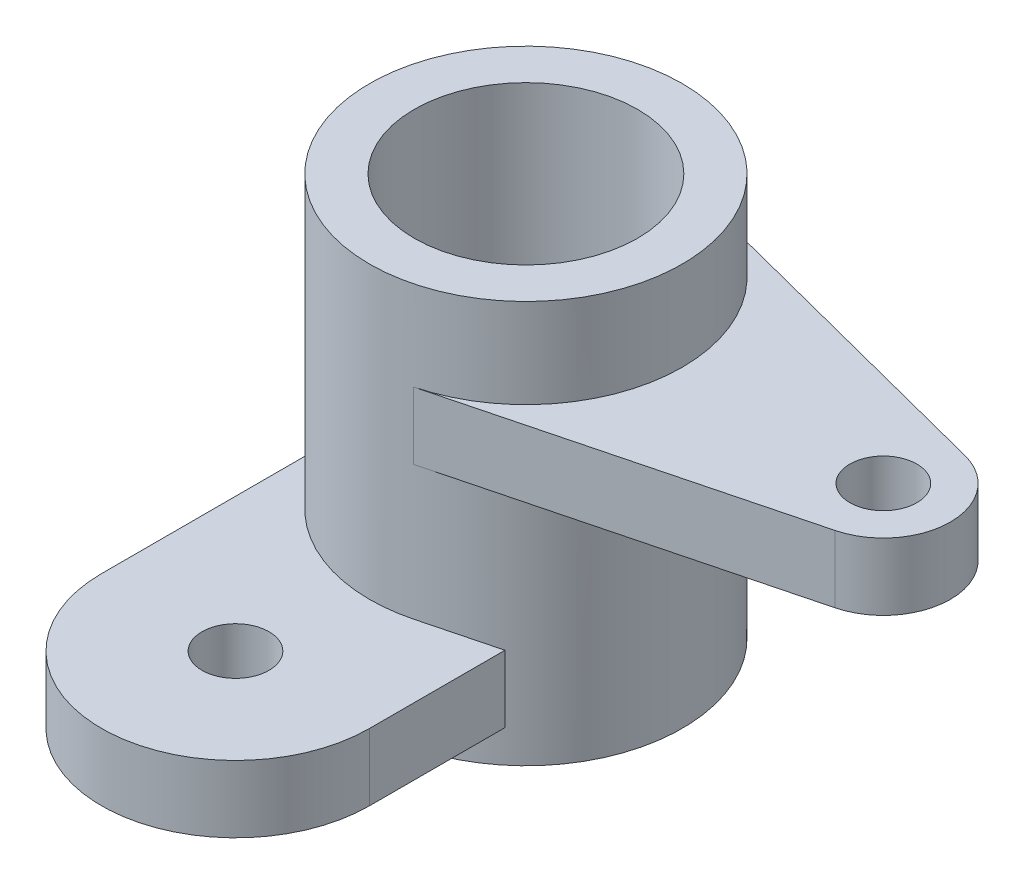
SolidWorks part; units mm, degrees
ref_plane "Front Plane" through (0, 0, 0) normal (0, 0, 1) x (1, 0, 0)
ref_plane "Top Plane" through (0, 0, 0) normal (0, 1, 0) x (1, 0, 0)
ref_plane "Right Plane" through (0, 0, 0) normal (1, 0, 0) x (0, 0, -1)
sketch "Sketch1" plane through (0, 0, 0) normal (0, 1, 0) x (1, 0, 0)
  line L0 (0, 0) -> (50000, 0) construction
  line L1 (0, 0) -> (0, 50000) construction
  line L2 (25, -60) -> (25, -24.4949)
  line L3 (-35, -60) -> (-35, 0)
  line L4 (83.75, -14.5237) -> (8.75, -33.8886)
  line L5 (83.75, 14.5237) -> (8.75, 33.8886)
  circle A0 centre (0, 0) radius 25
  circle A1 centre (0, 0) radius 35
  circle A2 centre (80, 0) radius 7.5
  circle A3 centre (80, 0) radius 15
  circle A4 centre (-5, -60) radius 7.5
  arc A5 (-35, -60) -> (25, -60) centre (-5, -60) ccw
  dimension "D1" = 70
  dimension "D2" = 50
  dimension "D3" = 30
  dimension "D4" = 15
  dimension "D6" = 5
  dimension "D7" = 60
  dimension "D8" = 15
  dimension "D5" = 80
  dimension "D9" = 60
extrude "Boss-Extrude1" add sketch "Sketch1" against normal blind 90 contours A1 A0 region at (17.021, 0, 29.4443)
extrude "Boss-Extrude2" add sketch "Sketch1<3>" against normal blind 15 from offset 20 contours A3 A2 | A3 A1 | A1 L4 L2 region at (21.0932, 0, 29.1879) region at (48.3793, 0, -0.4187) region at (65.4243, 0, 0) offset against normal yes
sketch "Sketch1<3>" plane through (0, 0, 0) normal (0, 1, 0) x (1, 0, 0) same geometry as "Sketch1"
extrude "Boss-Extrude3" add sketch "Sketch1<4>" against normal blind 15 from offset 65 contours L3 A5 L2 A1 A4 region at (-5, 0, 88.9183) offset against normal yes
sketch "Sketch1<4>" plane through (0, 0, 0) normal (0, 1, 0) x (1, 0, 0) same geometry as "Sketch1"
